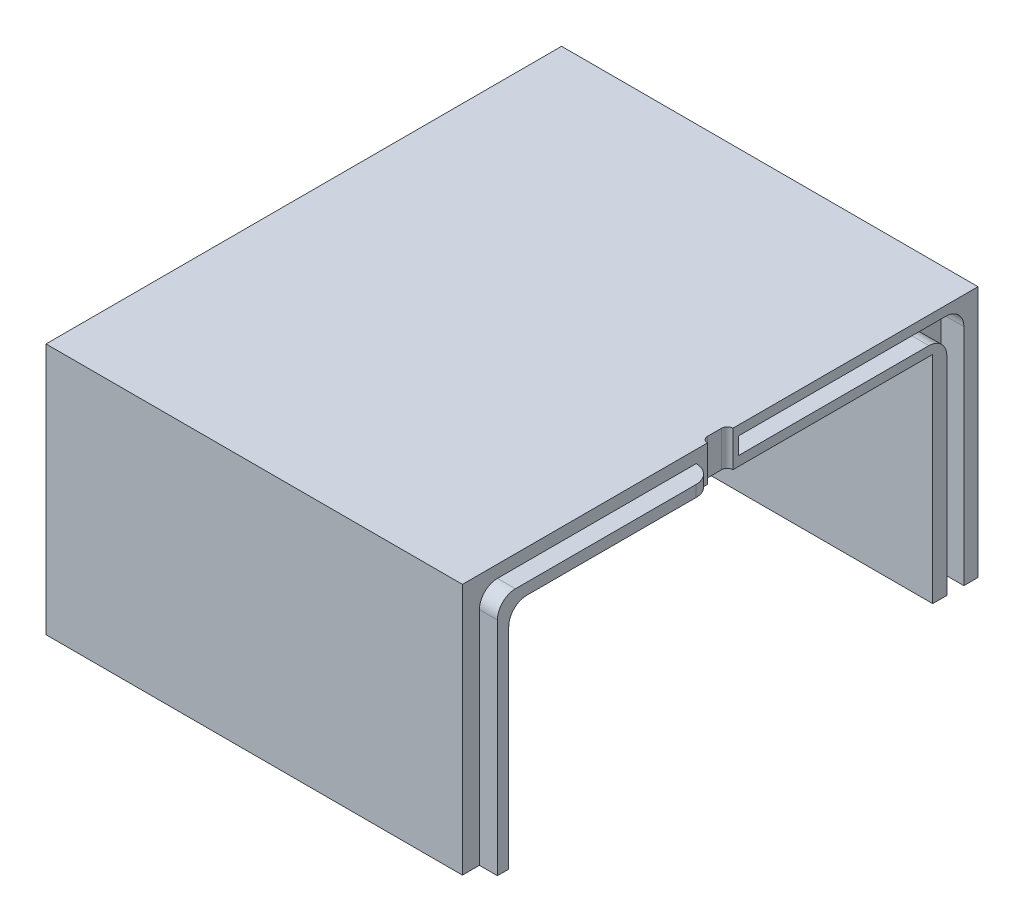
SolidWorks part; units mm, degrees
material "6061 Alloy"
ref_plane "Front Plane" through (0, 0, 0) normal (0, 0, 1) x (1, 0, 0)
ref_plane "Top Plane" through (0, 0, 0) normal (0, 1, 0) x (1, 0, 0)
ref_plane "Right Plane" through (0, 0, 0) normal (1, 0, 0) x (0, 0, -1)
sketch "MainSketch" plane through (0, 0, 0) normal (0, 1, 0) x (1, 0, 0)
  line L0 (0, -4) -> (-32.75, -4)
  line L1 (0, 0) -> (-36.75, 0)
  line L2 (0, 0) -> (0, -45.5)
  line L3 (0, -45.5) -> (-36.75, -45.5)
  line L4 (-36.75, 0) -> (-36.75, -45.5)
  line L5 (-32.75, -4) -> (-32.75, -41.5)
  line L6 (-32.75, -41.5) -> (0, -41.5)
  line L7 (31.75, -5) -> (-31.75, -5) construction
  line L8 (-31.75, -5) -> (-31.75, -40.5) construction
  line L9 (-31.75, -40.5) -> (31.75, -40.5) construction
  line L10 (0, -22.125) -> (0, -23.375) construction
  line L11 (0.5, -22.125) -> (0.5, -23.375)
  line L12 (-0.5, -22.125) -> (-0.5, -23.375)
  arc A0 (0.5, -22.125) -> (-0.5, -22.125) centre (0, -22.125) ccw
  arc A1 (-0.5, -23.375) -> (0.5, -23.375) centre (0, -23.375) ccw
  point P7 (-10, -2.5)
  point P10 (-34.25, -2.5)
  point P11 (-34.25, -43)
  point P12 (-10, -43)
  point P17 (0, -22.75)
  point P24 (-18.375, -2.5)
  point P26 (-18.375, -43)
  dimension "D14" = 0.5
  dimension "D1" = 4
  dimension "D2" = 4
  dimension "D3" = 4
  dimension "D4" = 36.75
  dimension "D6" = 5
  dimension "D7" = 5
  dimension "D8" = 5
  dimension "D9" = 2.5
  dimension "D10" = 2.5
  dimension "D11" = 10
  dimension "D12" = 10
  dimension "D13" = 2.5
  dimension "D15" = 1.25
  dimension "D5" = 35.5
  dimension "D16" = 63.5
  dimension "D17" = 18.375
extrude "Wall" add sketch "MainSketch" along normal blind 19.05 contours L6 L5 L0 L2 L1 L4 L3 region at (-16.375, 0, 3.4151)
extrude "Roof" add sketch "MainSketch<3>" along normal blind 3.175 from surface contours L5 L6 L2 L0 | L6 L5 L0 L2 L1 L4 L3 region at (-16.3884, 0, 22.75) region at (-16.375, 0, 3.4151) starting at face at (-17.375, 19.05, 22.75)
sketch "MainSketch<3>" plane through (0, 0, 0) normal (0, 1, 0) x (1, 0, 0) same geometry as "MainSketch"
hole_wizard "#2-56 Tapped Hole1" positions "3DSketch1" profile "Sketch2" tap size "#2-56" standard "ANSI Inch"
sketch3d "3DSketch1"
  point P19 (-18.375, 0, 43)
  point P22 (-18.375, 0, 2.5)
sketch "Sketch2" plane through (-18.375, 0, 43) normal (1, 0, 0) x (0, 0, -1)
  line L0 (0, 0) -> (0, 6.2642)
  line L1 (0, 6.2642) -> (0.889, 5.73)
  line L2 (0.889, 5.73) -> (0.889, 0)
  line L5 (0.889, 0) -> (0, 0)
  line L10 (0, 6.2642) -> (-0.889, 5.73) construction
  line L11 (0, -6.35) -> (0, 107.95) construction
  dimension "Tap Drill Dia." = 1.778
  dimension "Tap Drill Depth" = 5.73
  dimension "Drill Angle" = 118
cosmetic thread "Hole Thread1" parameters "D1"=4.37, "D2"=2.1844
cosmetic thread "Hole Thread2" parameters "D1"=4.37, "D2"=2.1844
sketch "Sketch3" plane through (0, 0, 0) normal (1, 0, 0) x (0, 0, -1)
  line L0 (-44, 0) -> (-44, 21.1375)
  line L1 (-41.5, 0) -> (-45.5, 0) construction
  line L2 (-44, 21.1375) -> (-24.875, 21.1375)
  line L3 (-1.25, 21.3875) -> (-1.25, 0)
  line L4 (0, 0) -> (-4, 0) construction
  line L5 (-43, 0) -> (-43, 20.1375)
  line L6 (-43, 20.1375) -> (-24.875, 20.1375)
  line L7 (-2.75, 19.8875) -> (-2.75, 0)
  line L8 (-44, 0) -> (-43, 0) construction
  line L9 (-45.5, 22.225) -> (-45.5, 0) construction
  line L10 (-2.75, 0) -> (-1.25, 0)
  line L11 (-21.125, 21.3875) -> (-1.25, 21.3875)
  line L12 (-21.125, 19.8875) -> (-21.125, 21.3875)
  line L13 (-45.5, 22.225) -> (-23.875, 22.225) construction
  line L14 (-23.875, 22.225) -> (-23.875, 19.05) construction
  line L15 (-44, 0) -> (-43, 0)
  line L16 (-24.875, 21.1375) -> (-24.875, 20.1375)
  line L18 (-21.125, 19.8875) -> (-2.75, 19.8875)
  line L19 (0, 22.225) -> (0, 0) construction
  line L20 (-21.625, 22.225) -> (-21.625, 19.05) construction
  line L21 (-21.625, 22.225) -> (0, 22.225) construction
  point P10 (-43.5, 0)
  point P17 (-2, 0)
  point P18 (-24.875, 20.6375)
  point P29 (-21.125, 21.5898)
  point P30 (-21.125, 20.6375)
  dimension "D2" = 1
  dimension "D4" = 2
  dimension "D7" = 1
  dimension "D1" = 1.5875
  dimension "D3" = 1
  dimension "D5" = 2
  dimension "D6" = 1.5
  dimension "D8" = 1.5
  dimension "D9" = 0.5
  dimension "D10" = 1.5875
extrude "Boss-Extrude1" add sketch "Sketch3" along normal blind 1.5875 contours L16 L2 L0 L15 L5 L6 region at (0, 10.5687, 43.7149)
extrude "Cut-Extrude3" cut sketch "Sketch3<3>" against normal blind 2 contours L12 L18 L7 L10 L3 L11 region at (0, 10.6937, 1.542)
sketch "Sketch3<3>" plane through (0, 0, 0) normal (1, 0, 0) x (0, 0, -1) same geometry as "Sketch3"
fillet "Fillet1" radius 1.5875 6 edges at (0.7937, 20.1375, 43) (0.7937, 21.1375, 44) (1.5875, 20.6375, 24.875) (-1, 21.3875, 1.25) (-1, 19.8875, 2.75) (-2, 20.6375, 21.125)
equation "\"D2@MainSketch\" = \"D1@MainSketch\""
equation "\"D3@MainSketch\" = \"D2@MainSketch\""
equation "\"D7@MainSketch\" = \"D6@MainSketch\""
equation "\"D8@MainSketch\" = \"D6@MainSketch\""
equation "\"D9@MainSketch\" = \"D7@MainSketch\" / 2"
equation "\"D10@MainSketch\" = \"D9@MainSketch\""
equation "\"D12@MainSketch\" = \"D11@MainSketch\""
equation "\"D13@MainSketch\" = \"D10@MainSketch\""
equation "\"D4@MainSketch\"=(\"D16@MainSketch\"+\"D6@MainSketch\"*2)/2"
equation "\"side_thick\"= 4"
equation "\"D1@MainSketch\"=\"side_thick\""
equation "\"top_thick\"=3.175"
equation "\"D1@Roof\"=\"top_thick\""
equation "\"D4@Sketch3\"=\"side_thick\"/2"
equation "\"D17@MainSketch\"=\"D4@MainSketch\"/2"
equation "\"D3@Sketch3\"=\"D2@Sketch3\""
equation "\"D8@Sketch3\"=\"D6@Sketch3\""
equation "\"D9@Sketch3\"=\"D6@Sketch3\"-\"D7@Sketch3\""
equation "\"D10@Sketch3\"=\"D1@Sketch3\""
